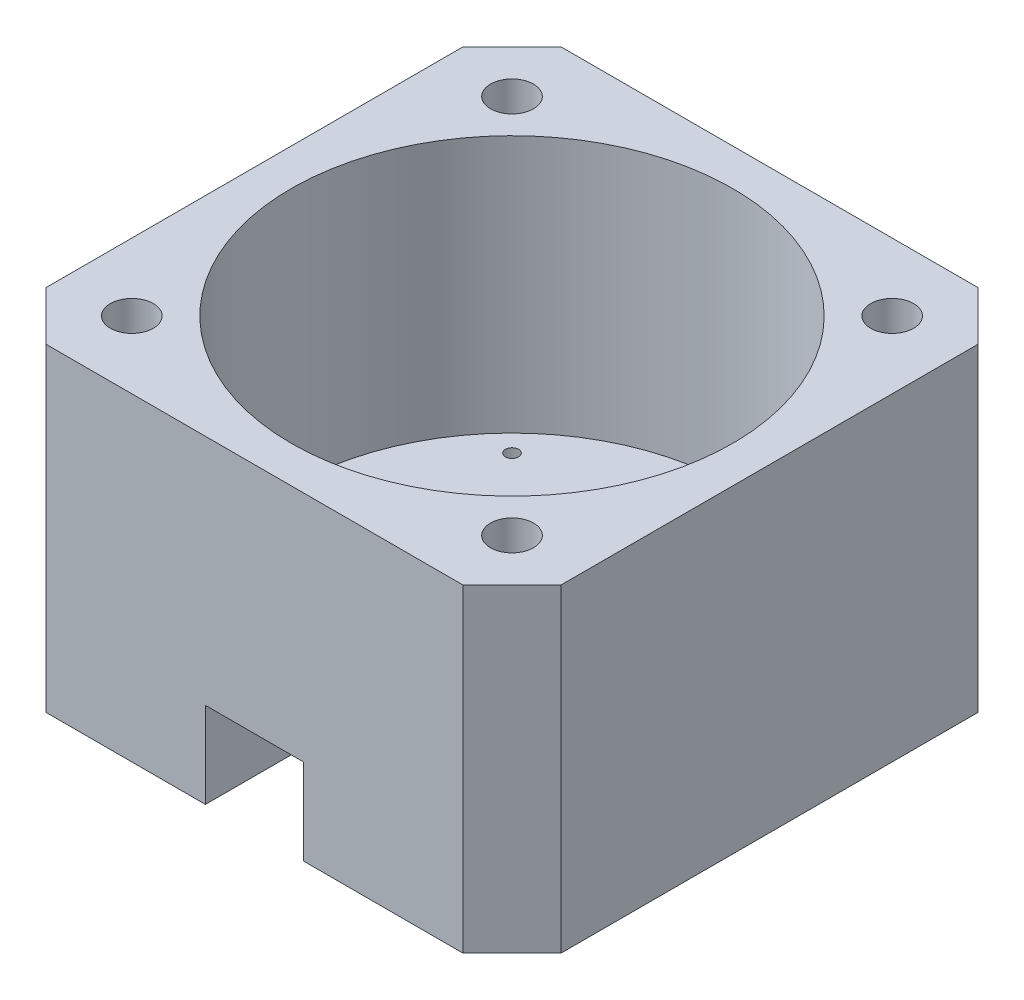
SolidWorks part; units mm, degrees
ref_plane "前视基准面" through (0, 0, 0) normal (0, 0, 1) x (1, 0, 0)
ref_plane "上视基准面" through (0, 0, 0) normal (0, 1, 0) x (1, 0, 0)
ref_plane "右视基准面" through (0, 0, 0) normal (1, 0, 0) x (0, 0, -1)
other "Configuration Table"
sketch "草图-尺寸参考" plane through (0, 0, 0) normal (0, 0, 1) x (1, 0, 0)
  line L1 (-6.8884, 22.2) -> (13.6066, 22.2) construction
  line L2 (-60.137, 0) -> (58.2604, 0) construction
  line L3 (-21, 20) -> (37.7214, 20) construction
  line L4 (-21, 20) -> (58.2604, 20) construction
  line L5 (-2.8262, 56) -> (1.944, 56) construction
  line L6 (-32.6672, 32) -> (36.6626, 32) construction
  line L7 (-40.6172, 38.8) -> (44.682, 38.8) construction
  line L8 (-21, 38.8) -> (58.2604, 38.8) construction
  line L9 (-21, 56) -> (58.2604, 56) construction
  line L10 (-40.6172, 5) -> (58.2604, 5) construction
  line L11 (-21, 32) -> (58.2604, 32) construction
  line L12 (15.1825, 35.4) -> (26.9517, 35.4) construction
  line L13 (-40.6172, 35.4) -> (26.9517, 35.4) construction
  line L14 (-40.6172, 38.8) -> (26.9517, 38.8) construction
  line L15 (-21, 22.2) -> (58.2604, 22.2) construction
  line L16 (2.984, 48.2) -> (7.9005, 48.2) construction
  line L17 (-6.8884, 48.2) -> (13.6066, 48.2) construction
  line L18 (0.4739, 32.2) -> (7.6251, 32.2) construction
  line L19 (15.1825, 5.4) -> (26.9517, 5.4) construction
  line L20 (-6.8884, 32.2) -> (13.6066, 32.2) construction
  line L21 (-21, 0) -> (58.2604, 0) construction
  line L22 (-60.137, 5) -> (58.2604, 5) construction
  point P4 (0.4739, 32.2)
  point P5 (7.6251, 32.2)
  dimension "D3" = 5
  dimension "D2" = 32
  dimension "D11" = 15
  dimension "D4" = 24
  dimension "D5" = 6.8
  dimension "D6" = 3.4
  dimension "D7" = 2.2
  dimension "D8" = 26
  dimension "D9" = 10
  dimension "D10" = 30
sketch "草图1" plane through (0, 0, 0) normal (0, 1, 0) x (1, 0, 0)
  line L0 (0, 64.5461) -> (0, -53.8448) construction
  line L1 (-21, -21) -> (21, -21)
  line L2 (-21, -21) -> (-21, 21)
  line L3 (-21, 21) -> (21, 21)
  line L4 (21, -21) -> (21, 21)
  line L5 (-21, -21) -> (21, 21) construction
  line L6 (-21, 21) -> (21, -21) construction
  line L7 (-56.9939, 0) -> (64.175, 0) construction
  line L8 (-15.5, 64.5461) -> (-15.5, -53.8448) construction
  line L9 (15.5, 64.5461) -> (15.5, -53.8448) construction
  line L10 (-56.9939, -15.5) -> (64.175, -15.5) construction
  line L11 (-56.9939, 15.5) -> (64.175, 15.5) construction
  circle A0 centre (-15.5, 15.5) radius 1.75
  circle A1 centre (15.5, 15.5) radius 1.75
  circle A2 centre (15.5, -15.5) radius 1.75
  circle A3 centre (-15.5, -15.5) radius 1.75
  circle A4 centre (0, 0.1912) radius 9.5 construction
  point P0 (0, 0)
  point P29 (0, 0)
  dimension "D7" = 3.5
  dimension "D9" = 19
  dimension "D1" = 42
  dimension "D2" = 42
  dimension "D3" = 15.5
  dimension "D4" = 15.5
  dimension "D5" = 15.5
  dimension "D6" = 15.5
  dimension "D8" = 4
extrude "凸台-拉伸1" add sketch "草图1" along normal blind 26
sketch "草图5" plane through (0, 0, 0) normal (0, -1, 0) x (1, 0, 0)
  line L0 (-21, -21) -> (21, 21) construction
  line L1 (-21, 21) -> (21, -21) construction
  line L3 (-21, -21) -> (21, 21) construction
  line L4 (-21, 21) -> (21, -21) construction
  circle A0 centre (0, -0.1912) radius 9.5 construction
  circle A1 centre (0, -0.1912) radius 9.5 construction
  point P3 (21, 21)
  point P37 (-6.6213, 6.6213)
  point P39 (6.6213, 6.6213)
  point P41 (6.8124, -6.8124)
  point P43 (-6.8124, -6.8124)
sketch "草图8" plane through (0, 0, 0) normal (0, -1, 0) x (1, 0, 0)
  circle A1 centre (0, 0) radius 6.5
  dimension "D1" = 13
extrude "切除-拉伸1" cut sketch "草图8" against normal through all
sketch "草图9" plane through (0, 0, 0) normal (0, -1, 0) x (1, 0, 0)
  line L0 (-21, 21) -> (21, -21) construction
  line L1 (-21, -21) -> (21, 21) construction
  line L2 (-21, 21) -> (21, -21) construction
  line L3 (-21, -21) -> (21, 21) construction
  circle A0 centre (0, 0) radius 16 construction
  point P12 (-11.3137, 11.3137)
  point P16 (11.3137, -11.3137)
  point P18 (11.3137, 11.3137)
  point P23 (-11.3137, -11.3137)
  dimension "D1" = 32
hole_wizard "Ø4.4 (4.4) 直径孔1" positions "草图9" profile "草图11" hole size "Ø4.4" standard "GB"
sketch "草图11" plane through (-11.3137, 0, -11.3137) normal (1, 0, 0) x (0, 0, -1)
  line L0 (0, 0) -> (0, 5.3219)
  line L1 (0, 5.3219) -> (2.2, 4)
  line L2 (2.2, 4) -> (2.2, 0)
  line L5 (2.2, 0) -> (0, 0)
  line L10 (0, 5.3219) -> (-2.2, 4) construction
  line L11 (0, -6.35) -> (0, 107.95) construction
  dimension "孔直径" = 4.4
  dimension "孔深度" = 4
  dimension "导头角度" = 118
sketch "草图13" plane through (0, 26, 0) normal (0, 1, 0) x (1, 0, 0)
  circle A0 centre (0, 0) radius 18
  dimension "D1" = 36
extrude "切除-拉伸2" cut sketch "草图13" against normal blind 21
chamfer "倒角1" distance 4 angle 45 4 edges at (-21, 13, 21) (21, 13, 21) (21, 13, -21) (-21, 13, -21)
sketch "草图14" plane through (0, 0, 0) normal (0, -1, 0) x (1, 0, 0)
  line L0 (0, -64.5461) -> (0, 53.8448) construction
  line L1 (-4, 23) -> (4, 23)
  line L2 (-4, 23) -> (-4, 13)
  line L3 (-4, 13) -> (4, 13)
  line L4 (4, 23) -> (4, 13)
  line L5 (-4, 23) -> (4, 13) construction
  line L6 (-4, 13) -> (4, 23) construction
  circle A0 centre (0, 0) radius 18 construction
  point P0 (0, 18)
  dimension "D1" = 8
  dimension "D2" = 10
extrude "切除-拉伸3" cut sketch "草图14" against normal blind 7
hole_wizard "M2.5 六角圆柱头螺钉的柱形沉头孔1" positions "草图5" profile "草图15" counterbore size "M2.5" standard "GB" end condition through all
sketch "草图15" plane through (-6.8124, 0, -6.8124) normal (1, 0, 0) x (0, 0, -1)
  line L0 (0, 0) -> (0, 26)
  line L1 (0, 26) -> (1.35, 26)
  line L3 (1.35, 26) -> (1.35, 2.5)
  line L4 (1.35, 2.5) -> (2.5, 2.5)
  line L5 (2.5, 2.5) -> (2.5, 0)
  line L7 (2.5, 0) -> (0, 0)
  line L11 (0, -6.35) -> (0, 107.95) construction
  dimension "通孔孔直径" = 2.7
  dimension "通孔孔深度" = 26
  dimension "柱形沉头孔直径" = 5
  dimension "柱形沉头孔深度" = 2.5
